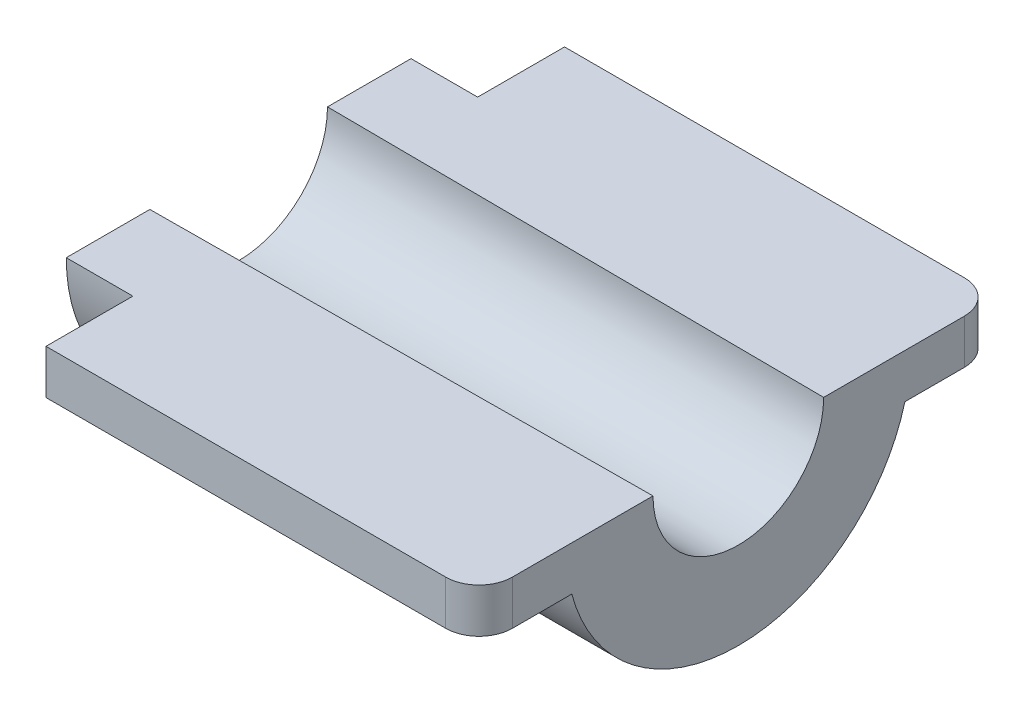
SolidWorks part; units mm, degrees
material "ABS"
ref_plane "Front Plane" through (0, 0, 0) normal (0, 0, 1) x (1, 0, 0)
ref_plane "Top Plane" through (0, 0, 0) normal (0, 1, 0) x (1, 0, 0)
ref_plane "Right Plane" through (0, 0, 0) normal (1, 0, 0) x (0, 0, -1)
sketch "Sketch1" plane through (0, 0, 0) normal (1, 0, 0) x (0, 0, -1)
  line L0 (-16.35, 0) -> (16.35, 0)
  line L1 (-9, 0) -> (9, 0)
  line L2 (-9, 0) -> (-23.35, 0)
  line L4 (-15, -4) -> (-23.35, -4)
  line L5 (-23.35, 0) -> (-23.35, -4)
  line L6 (9, 0) -> (23.35, 0)
  line L8 (15, -4) -> (23.35, -4)
  line L9 (23.35, 0) -> (23.35, -4)
  arc A1 (-15, -4) -> (15, -4) centre (0, 0) ccw
  dimension "D3" = 4
  dimension "D4" = 4
extrude "Boss-Extrude1" add sketch "Sketch1" along normal blind 35 contours L4 A1 L8 L9 L6 L0 L2 L5 region at (0, -5.9283, 0)
sketch "Sketch2" plane through (0, 0, 0) normal (-1, 0, 0) x (0, 0, 1)
  line L0 (-15.5242, 0) -> (0, 0)
  line L1 (23.35, 0) -> (-23.35, 0) construction
  circle A1 centre (0, 0) radius 15.5242
  arc A2 (-15, -4) -> (15, -4) centre (0, 0) ccw construction
  line M3 (23.35, 0) -> (-23.35, 0)
  line M5 (23.35, 0) -> (-23.35, 0)
  arc M8 (-15, -4) -> (15, -4) centre (0, 0) ccw
  dimension "D1" = 0
extrude "Boss-Extrude2" add sketch "Sketch2" along normal blind 10 contours A1 M5 M8 M3 region at (0, -6.5887, 0)
fillet "Fillet1" radius 3 1 edges at (35, -2, 23.35) type face fillet first side face at (35, -4.5874, 0) second side face at (17.5, -2, 23.35)
fillet "Fillet3" radius 3 1 edges at (35, -2, -23.35) type face fillet first side face at (17.5, -2, -23.35) second side face at (35, -4.5874, -1)
sketch "Sketch3" plane through (0, 0, 0) normal (-1, 0, 0) x (0, 0, 1)
  line L0 (-15.5242, 0) -> (-23.35, 0)
  line L1 (-23.35, 0) -> (-23.35, -4)
  line L2 (-23.35, -4) -> (-15, -4)
  line L3 (0, 8.007) -> (0, -24.2317) construction
  line L4 (23.35, -4) -> (15, -4)
  line L5 (23.35, 0) -> (23.35, -4)
  line L6 (15.5242, 0) -> (23.35, 0)
  arc A0 (-15.5242, 0) -> (-15, -4) centre (0, 0) ccw
  arc A1 (15.5242, 0) -> (15, -4) centre (0, 0) cw
extrude "Boss-Extrude3" add sketch "Sketch3" along normal blind 4
sketch "Sketch4" plane through (-10, 0, 0) normal (-1, 0, 0) x (0, 0, 1)
  circle A0 centre (0, 0) radius 8
  dimension "D1" = 16
extrude "Cut-Extrude7" cut sketch "Sketch4" against normal through all draft 0.4
